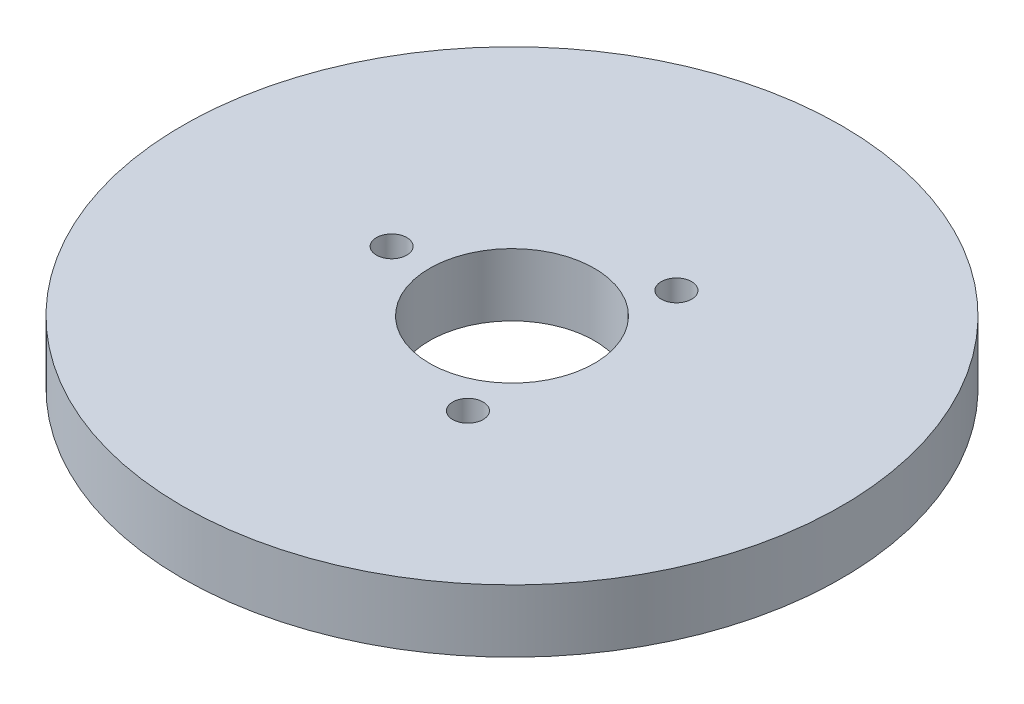
SolidWorks part; units mm, degrees
ref_plane "Front Plane" through (0, 0, 0) normal (0, 0, 1) x (1, 0, 0)
ref_plane "Top Plane" through (0, 0, 0) normal (0, 1, 0) x (1, 0, 0)
ref_plane "Right Plane" through (0, 0, 0) normal (1, 0, 0) x (0, 0, -1)
sketch "Sketch1" plane through (0, 0, 0) normal (0, 1, 0) x (1, 0, 0)
  circle A0 centre (0, 0) radius 100
  dimension "FLANGE_OD" = 200
extrude "Boss-Extrude1" add sketch "Sketch1" along normal blind 19
sketch "Sketch2" plane through (0, 0, 0) normal (0, 1, 0) x (1, 0, 0)
  circle A0 centre (0, 0) radius 25
  dimension "BORE_D" = 50
extrude "Cut-Extrude1" cut sketch "Sketch2" along normal through all
sketch "Sketch3" plane through (0, 19, 0) normal (0, 1, 0) x (1, 0, 0)
  circle A0 centre (0, 0) radius 36.5258 construction
  circle A1 centre (-36.5258, 0) radius 4.622
  dimension "BOLT_D" = 9.2441
  dimension "BOLT_PCD" = 73.0516
extrude "Cut-Extrude2" cut sketch "Sketch3" against normal blind 12.6602
pattern_circular "CirPattern1" count 3 over 360 about axis through (0, 0, 0) along (0, 1, 0) of "Cut-Extrude2"
